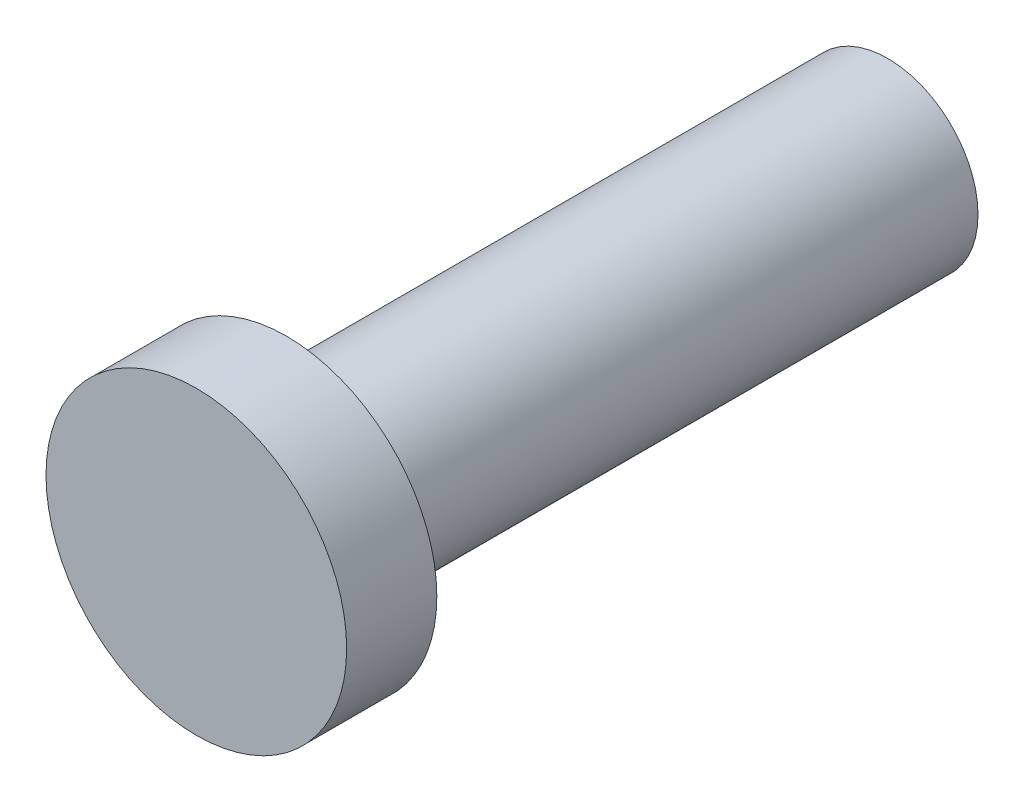
SolidWorks part; units mm, degrees
ref_plane "Alzado" through (0, 0, 0) normal (0, 0, 1) x (1, 0, 0)
ref_plane "Planta" through (0, 0, 0) normal (0, 1, 0) x (1, 0, 0)
ref_plane "Vista lateral" through (0, 0, 0) normal (1, 0, 0) x (0, 0, -1)
sketch "Croquis1" plane through (0, 0, 0) normal (0, 0, 1) x (1, 0, 0)
  circle A0 centre (0, 0) radius 2.5
  circle A1 centre (0, 0) radius 1.5
  dimension "D1" = 5
  dimension "D2" = 3
extrude "Saliente-Extruir1" add sketch "Croquis1" along normal blind 1.5 contours A0 | A1 A0 region at (-2.4293, 0, 0) region at (0, 0, 0)
extrude "Saliente-Extruir2" add sketch "Croquis1<3>" against normal blind 10 contours A1 region at (0, 0, 0)
sketch "Croquis1<3>" plane through (0, 0, 0) normal (0, 0, 1) x (1, 0, 0) same geometry as "Croquis1"
